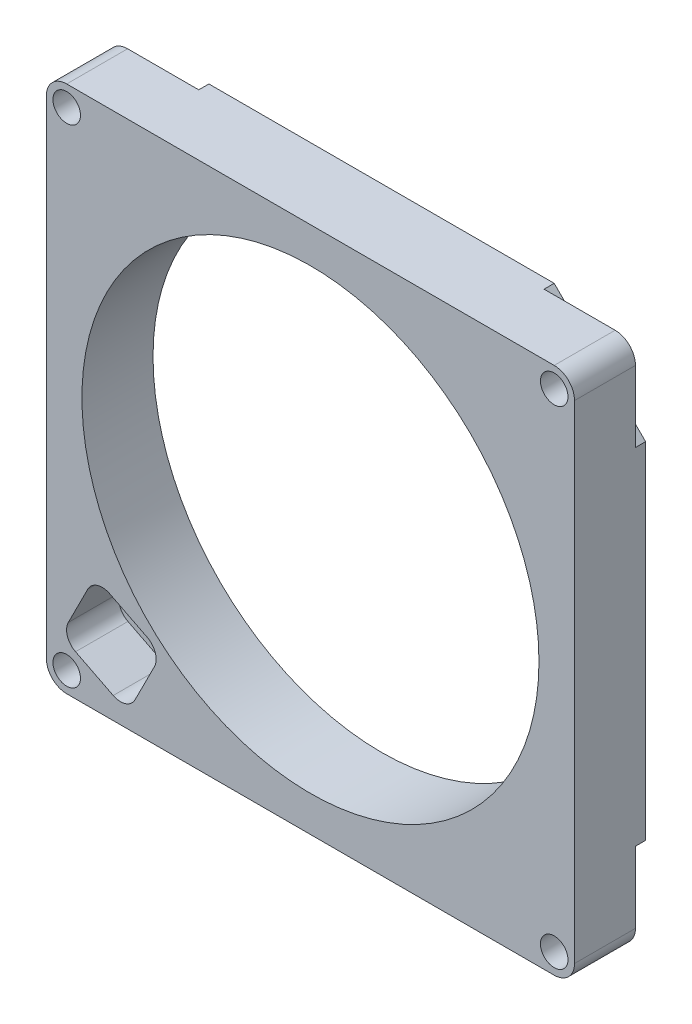
SolidWorks part; units mm, degrees
material "PET"
ref_plane "Front Plane" through (0, 0, 0) normal (0, 0, 1) x (1, 0, 0)
ref_plane "Top Plane" through (0, 0, 0) normal (0, 1, 0) x (1, 0, 0)
ref_plane "Right Plane" through (0, 0, 0) normal (1, 0, 0) x (0, 0, -1)
sketch "Sketch1" plane through (0, 0, 0) normal (0, 0, 1) x (1, 0, 0)
  line L8 (-213.995, 2363.8407) -> (-213.995, 2440.0407)
  line L9 (-217.17, 2443.2157) -> (-293.37, 2443.2157)
  line L10 (-296.545, 2440.0407) -> (-296.545, 2363.8407)
  line L11 (-293.37, 2360.6657) -> (-217.17, 2360.6657)
  arc A8 (-217.17, 2360.6657) -> (-213.995, 2363.8407) centre (-217.17, 2363.8407) ccw
  arc A9 (-213.995, 2440.0407) -> (-217.17, 2443.2157) centre (-217.17, 2440.0407) ccw
  arc A10 (-293.37, 2443.2157) -> (-296.545, 2440.0407) centre (-293.37, 2440.0407) ccw
  arc A11 (-296.545, 2363.8407) -> (-293.37, 2360.6657) centre (-293.37, 2363.8407) ccw
extrude "Boss-Extrude1" add sketch "Sketch1" against normal up to surface (7.9375 mm away)
sketch "Sketch2" plane through (0, 0, -7.9375) normal (0, 0, -1) x (-1, 0, 0)
  line L16 (282.2575, 2360.6657) -> (296.545, 2374.9532)
  line L17 (296.545, 2374.9532) -> (296.545, 2428.9282)
  line L18 (296.545, 2428.9282) -> (282.2575, 2443.2157)
  line L19 (282.2575, 2443.2157) -> (228.2825, 2443.2157)
  line L20 (228.2825, 2443.2157) -> (213.995, 2428.9282)
  line L21 (213.995, 2428.9282) -> (213.995, 2374.9532)
  line L22 (213.995, 2374.9532) -> (228.2825, 2360.6657)
  line L23 (228.2825, 2360.6657) -> (282.2575, 2360.6657)
  circle A1 centre (255.27, 2401.9407) radius 35.7188
extrude "Boss-Extrude2" add sketch "Sketch2" along normal blind 1.5875
sketch "Sketch3" plane through (0, 0, -7.9375) normal (0, 0, -1) x (-1, 0, 0)
  circle A1 centre (255.27, 2401.9407) radius 35.7188
  circle A2 centre (255.27, 2401.9407) radius 35.7188
  dimension "D1" = 0
extrude "Cut-Extrude1" cut sketch "Sketch3" against normal through all and the other way through all
hole_wizard "#6 Clearance Hole1" positions "Sketch5" profile "Sketch4" hole size "#6" standard "ANSI Inch" end condition through all
sketch "Sketch5" plane through (0, 0, -7.9375) normal (0, 0, -1) x (-1, 0, 0)
  point P0 (217.17, 2440.0407)
  point P2 (293.37, 2440.0407)
  point P4 (293.37, 2363.8407)
  point P6 (217.17, 2363.8407)
sketch "Sketch4" plane through (-217.17, 2440.0407, -7.9375) normal (1, 0, 0) x (0, 1, 0)
  line L0 (0, 0) -> (0, 7.9375)
  line L1 (0, 7.9375) -> (2.1526, 7.9375)
  line L2 (2.1526, 7.9375) -> (2.1526, 0)
  line L5 (2.1526, 0) -> (0, 0)
  line L11 (0, -6.35) -> (0, 107.95) construction
  dimension "Thru Hole Dia." = 4.3053
  dimension "Thru Hole Depth" = 7.9375
sketch "Sketch6" plane through (0, 0, 0) normal (0, 0, 1) x (1, 0, 0)
  line L0 (-286.0983, 2364.0731) -> (-291.989, 2367.0475)
  line L1 (-282.6861, 2365.1956) -> (-279.6585, 2371.1918)
  line L2 (-293.1115, 2370.4597) -> (-290.0839, 2376.4558)
  line L3 (-280.781, 2374.604) -> (-286.6717, 2377.5783)
  line L4 (-283.831, 2362.9283) -> (-288.939, 2378.7232) construction
  line L5 (-294.2563, 2368.1923) -> (-278.5137, 2373.4591) construction
  line L6 (-286.385, 2370.8257) -> (-291.5977, 2373.4577) construction
  arc A0 (-279.6585, 2371.1918) -> (-280.781, 2374.604) centre (-281.9259, 2372.3366) ccw
  arc A1 (-282.6861, 2365.1956) -> (-286.0983, 2364.0731) centre (-284.9535, 2366.3405) cw
  arc A2 (-290.0839, 2376.4558) -> (-286.6717, 2377.5783) centre (-287.8165, 2375.311) cw
  arc A3 (-291.989, 2367.0475) -> (-293.1115, 2370.4597) centre (-290.8441, 2369.3148) cw
  point P0 (-291.5977, 2373.4577)
  point P2 (-286.385, 2370.8257)
  dimension "D1" = 2.54
extrude "Cut-Extrude2" cut sketch "Sketch6" against normal offset from surface (6.604 mm away) 2.921 up to face at (-255.27, 2401.9407, -9.525)
hole_wizard "F (0.257) Diameter Hole1" positions "Sketch8" profile "Sketch7" hole size "F" standard "ANSI Inch" end condition through all
sketch "Sketch8" plane through (0, 0, -9.525) normal (0, 0, -1) x (-1, 0, 0)
  point P0 (286.385, 2370.8257)
sketch "Sketch7" plane through (-286.385, 2370.8257, -9.525) normal (1, 0, 0) x (0, 1, 0)
  line L0 (0, 0) -> (0, 9.525)
  line L1 (0, 9.525) -> (3.2639, 9.525)
  line L2 (3.2639, 9.525) -> (3.2639, 0)
  line L5 (3.2639, 0) -> (0, 0)
  line L11 (0, -6.35) -> (0, 107.95) construction
  dimension "Thru Hole Dia." = 6.5278
  dimension "Thru Hole Depth" = 9.525
hole_wizard "#51 (0.067) Diameter Hole1" positions "Sketch9" profile "Sketch10" hole size "#51" standard "ANSI Inch" end condition through all
sketch "Sketch9" plane through (0, 0, -9.525) normal (0, 0, -1) x (-1, 0, 0)
  point P0 (290.6199, 2373.0045)
sketch "Sketch10" plane through (-290.6199, 2373.0045, -9.525) normal (1, 0, 0) x (0, 1, 0)
  line L0 (0, 0) -> (0, 9.525)
  line L1 (0, 9.525) -> (0.8509, 9.525)
  line L2 (0.8509, 9.525) -> (0.8509, 0)
  line L5 (0.8509, 0) -> (0, 0)
  line L11 (0, -6.35) -> (0, 107.95) construction
  dimension "Thru Hole Dia." = 1.7018
  dimension "Thru Hole Depth" = 9.525
sketch "Sketch11" plane through (0, 0, 0) normal (0, 0, 1) x (1, 0, 0)
  line L4 (-213.995, 2363.8407) -> (-213.995, 2440.0407)
  line L5 (-217.17, 2443.2157) -> (-293.37, 2443.2157)
  line L6 (-296.545, 2440.0407) -> (-296.545, 2363.8407)
  line L7 (-293.37, 2360.6657) -> (-217.17, 2360.6657)
  line L8 (-213.995, 2363.8407) -> (-213.995, 2440.0407)
  line L9 (-217.17, 2443.2157) -> (-293.37, 2443.2157)
  line L10 (-296.545, 2440.0407) -> (-296.545, 2363.8407)
  line L11 (-293.37, 2360.6657) -> (-217.17, 2360.6657)
  line L13 (-280.781, 2374.604) -> (-286.6717, 2377.5783)
  line L14 (-282.6861, 2365.1956) -> (-279.6585, 2371.1918)
  line L15 (-291.989, 2367.0475) -> (-286.0983, 2364.0731)
  line L16 (-290.0839, 2376.4558) -> (-293.1115, 2370.4597)
  line L17 (-280.781, 2374.604) -> (-286.6717, 2377.5783)
  line L18 (-282.6861, 2365.1956) -> (-279.6585, 2371.1918)
  line L19 (-291.989, 2367.0475) -> (-286.0983, 2364.0731)
  line L20 (-290.0839, 2376.4558) -> (-293.1115, 2370.4597)
  circle A0 centre (-293.37, 2363.8407) radius 2.1526 construction
  circle A1 centre (-255.27, 2401.9407) radius 35.7188 construction
  circle A2 centre (-217.17, 2363.8407) radius 2.1527 construction
  circle A3 centre (-217.17, 2440.0407) radius 2.1527 construction
  arc A4 (-217.17, 2360.6657) -> (-213.995, 2363.8407) centre (-217.17, 2363.8407) ccw
  arc A5 (-213.995, 2440.0407) -> (-217.17, 2443.2157) centre (-217.17, 2440.0407) ccw
  arc A6 (-293.37, 2443.2157) -> (-296.545, 2440.0407) centre (-293.37, 2440.0407) ccw
  arc A7 (-296.545, 2363.8407) -> (-293.37, 2360.6657) centre (-293.37, 2363.8407) ccw
  arc A8 (-217.17, 2360.6657) -> (-213.995, 2363.8407) centre (-217.17, 2363.8407) ccw
  arc A9 (-213.995, 2440.0407) -> (-217.17, 2443.2157) centre (-217.17, 2440.0407) ccw
  arc A10 (-293.37, 2443.2157) -> (-296.545, 2440.0407) centre (-293.37, 2440.0407) ccw
  arc A11 (-296.545, 2363.8407) -> (-293.37, 2360.6657) centre (-293.37, 2363.8407) ccw
  circle A12 centre (-293.37, 2440.0407) radius 2.1526 construction
  circle A13 centre (-293.37, 2363.8407) radius 2.1526
  circle A14 centre (-255.27, 2401.9407) radius 35.7188
  circle A15 centre (-217.17, 2363.8407) radius 2.1526
  circle A16 centre (-217.17, 2440.0407) radius 2.1526
  circle A17 centre (-293.37, 2440.0407) radius 2.1526
  arc A22 (-279.6585, 2371.1918) -> (-280.781, 2374.604) centre (-281.9259, 2372.3366) ccw
  arc A23 (-286.0983, 2364.0731) -> (-282.6861, 2365.1956) centre (-284.9535, 2366.3405) ccw
  arc A24 (-293.1115, 2370.4597) -> (-291.989, 2367.0475) centre (-290.8441, 2369.3148) ccw
  arc A25 (-286.6717, 2377.5783) -> (-290.0839, 2376.4558) centre (-287.8165, 2375.311) ccw
  arc A26 (-279.6585, 2371.1918) -> (-280.781, 2374.604) centre (-281.9259, 2372.3366) ccw
  arc A27 (-286.0983, 2364.0731) -> (-282.6861, 2365.1956) centre (-284.9535, 2366.3405) ccw
  arc A28 (-293.1115, 2370.4597) -> (-291.989, 2367.0475) centre (-290.8441, 2369.3148) ccw
  arc A29 (-286.6717, 2377.5783) -> (-290.0839, 2376.4558) centre (-287.8165, 2375.311) ccw
  dimension "D1" = 0
  dimension "D2" = 0
extrude "Boss-Extrude3" add sketch "Sketch11" along normal blind 1.5875
